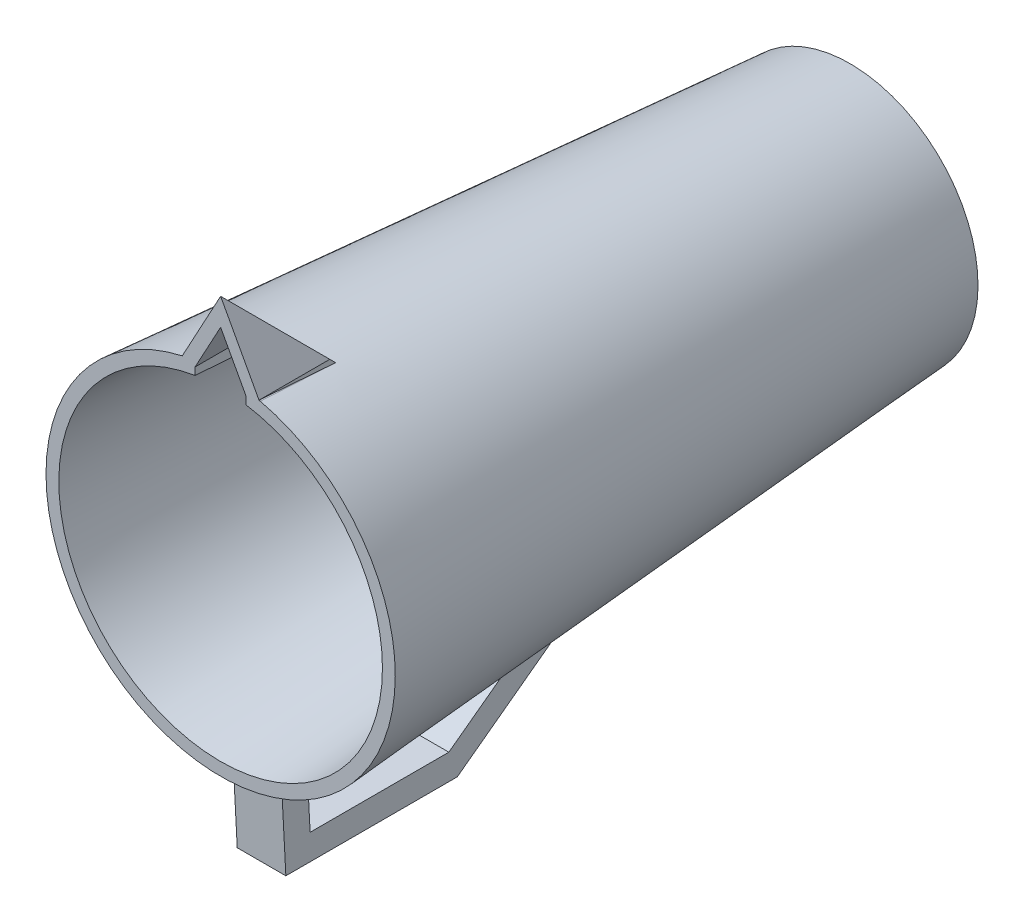
SolidWorks part; units mm, degrees
ref_plane "Alzado" through (0, 0, 0) normal (1, 0, 0) x (0, 1, 0)
ref_plane "Planta" through (0, 0, 0) normal (0, 0, 1) x (0, 1, 0)
ref_plane "Vista lateral" through (0, 0, 0) normal (0, 1, 0) x (-1, 0, 0)
sketch "Croquis1" plane through (0, 0, 0) normal (1, 0, 0) x (0, 1, 0)
  line L0 (0, 0) -> (0, 246) construction
  line L1 (0, 0) -> (-50, 0)
  line L2 (-50, 0) -> (-68.25, 246)
  line L3 (-68.25, 246) -> (0, 246)
  line L4 (0, 0) -> (0, 246)
  dimension "D1" = 100
  dimension "D2" = 246
  dimension "D3" = 136.5
revolve "Revolución1" add sketch "Croquis1" angle 360 about L0
sketch "Croquis2" plane through (0, 0, 0) normal (1, 0, 0) x (0, 1, 0)
  line L0 (-66.4714, 222.0251) -> (-95.1593, 220.5216)
  line L1 (-68.25, 246) -> (-50, 0) construction
  line L2 (-95.1593, 220.5216) -> (-95.1593, 166.3091)
  line L3 (-95.1593, 166.3091) -> (-58.6813, 117.0188)
  line L4 (-67.2114, 232) -> (-105.1593, 230.0112)
  line L5 (-105.1593, 230.0112) -> (-105.1593, 163.0112)
  line L6 (-105.1593, 163.0112) -> (-57.2952, 98.3358)
  line L7 (-67.229, 231.9991) -> (-105.1593, 230.0112) construction
  line L8 (-66.7057, 222.0128) -> (-95.1593, 220.5216) construction
  line L9 (-67.2114, 232) -> (-66.4714, 222.0251) construction
  line L10 (-105.1593, 163.0112) -> (-66.7194, 111.0701) construction
  line L11 (-58.6813, 117.0188) -> (-57.2952, 98.3358) construction
  line L12 (68.25, 246) -> (-68.25, 246) construction
  line L13 (-67.2114, 232) -> (-65.2137, 232.1047)
  line L14 (-65.2137, 232.1047) -> (-64.4736, 222.1298)
  line L15 (-64.4736, 222.1298) -> (-66.4714, 222.0251)
  line L16 (-57.2952, 98.3358) -> (-55.0663, 95.324)
  line L17 (-55.0663, 95.324) -> (-56.4523, 114.007)
  line L18 (-56.4523, 114.007) -> (-58.6813, 117.0188)
  dimension "D2" = 134
  dimension "D3" = 38
  dimension "D4" = 67
  dimension "D5" = 3
  dimension "D6" = 14
  dimension "D7" = 2
  dimension "D1" = 10
extrude "Saliente-Extruir1" add sketch "Croquis2" along normal mid plane 19
sketch "Croquis5" plane through (0, 0, 0) normal (1, 0, 0) x (0, 1, 0)
  line L0 (64.25, 246) -> (94.25, 246)
  line L1 (68.25, 246) -> (-68.25, 246) construction
  line L2 (94.25, 246) -> (64.25, 216)
  line L3 (64.25, 216) -> (64.25, 246)
  line L4 (50, 0) -> (68.25, 246) construction
  point P5 (68.25, 246)
  dimension "D1" = 45
  dimension "D2" = 4
  dimension "D3" = 30
extrude "Saliente-Extruir6" add sketch "Croquis5" along normal mid plane 30
sketch "Croquis6" plane through (0, 0, 246) normal (0, 0, 1) x (1, 0, 0)
  line L0 (-15, 66.5812) -> (0, 94.25)
  line L1 (15, 94.25) -> (-15, 94.25) construction
  line L2 (0, 94.25) -> (15, 66.5812)
  line L3 (15, 66.5812) -> (15, 98.25)
  line L4 (15, 98.25) -> (-15, 98.25)
  line L5 (-15, 98.25) -> (-15, 66.5812)
  dimension "D1" = 4
extrude "Cortar-Extruir1" cut sketch "Croquis6" against normal blind 30
shell "Vaciado1" thickness 5 removed face at (0, 30.8604, 246)
